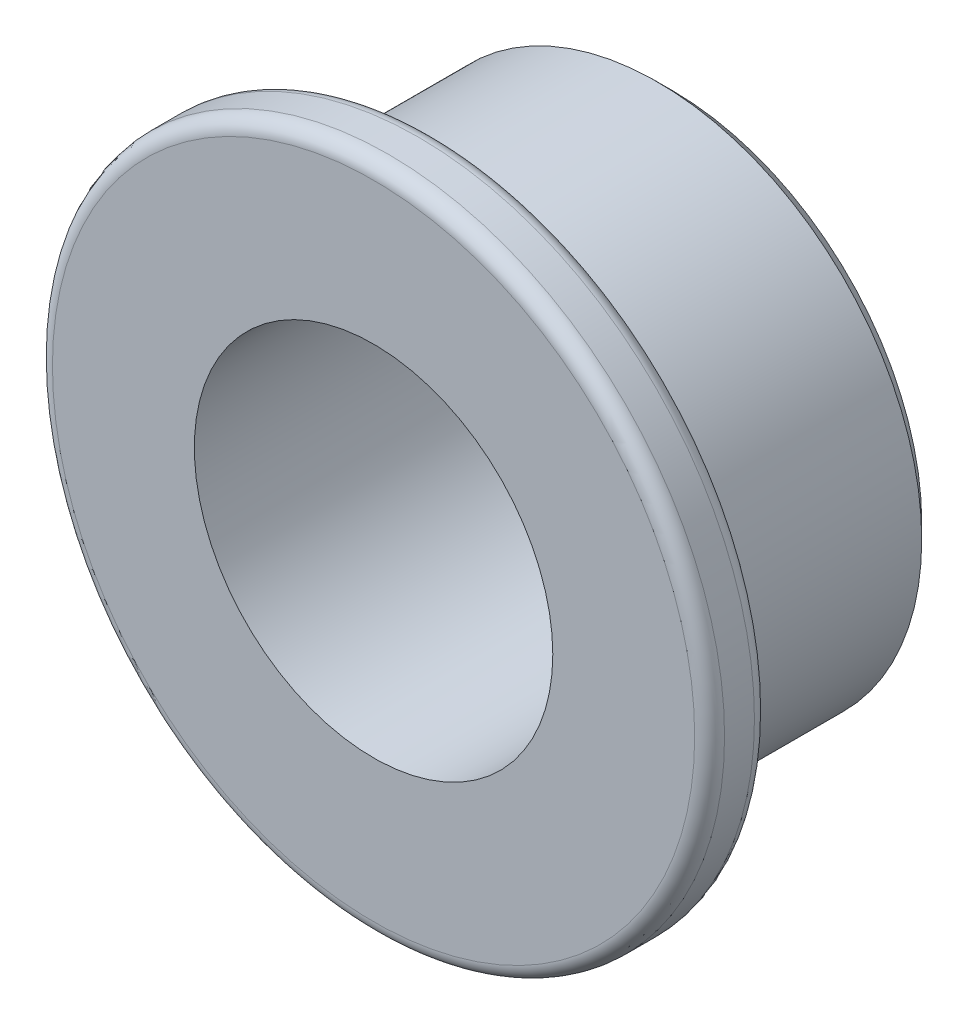
SolidWorks part; units mm, degrees
ref_plane "Front Plane" through (0, 0, 0) normal (0, 0, 1) x (1, 0, 0)
ref_plane "Top Plane" through (0, 0, 0) normal (0, 1, 0) x (1, 0, 0)
ref_plane "Right Plane" through (0, 0, 0) normal (1, 0, 0) x (0, 0, -1)
sketch "Sketch1" plane through (0, 0, 0) normal (0, 0, 1) x (1, 0, 0)
  circle A0 centre (0, 0) radius 8.85
  circle A1 centre (0, 0) radius 6
  dimension "D1" = 17.7
  dimension "D2" = 12
extrude "Boss-Extrude1" add sketch "Sketch1" against normal blind 8
sketch "Sketch2" plane through (0, 0, 0) normal (0, 0, 1) x (1, 0, 0)
  circle A0 centre (0, 0) radius 11.25
  circle A1 centre (0, 0) radius 6
  dimension "D1" = 22.5
extrude "Boss-Extrude2" add sketch "Sketch2" along normal blind 2
fillet "Fillet1" radius 0.5 1 edges at (11.25, 0, 2)
fillet "Fillet2" radius 0.5 1 edges at (11.25, 0, 0)
fillet "Fillet3" radius 0.8 1 edges at (8.85, 0, 0)
chamfer "Chamfer1" distance 0.5 angle 45 1 edges at (8.85, 0, -8)
